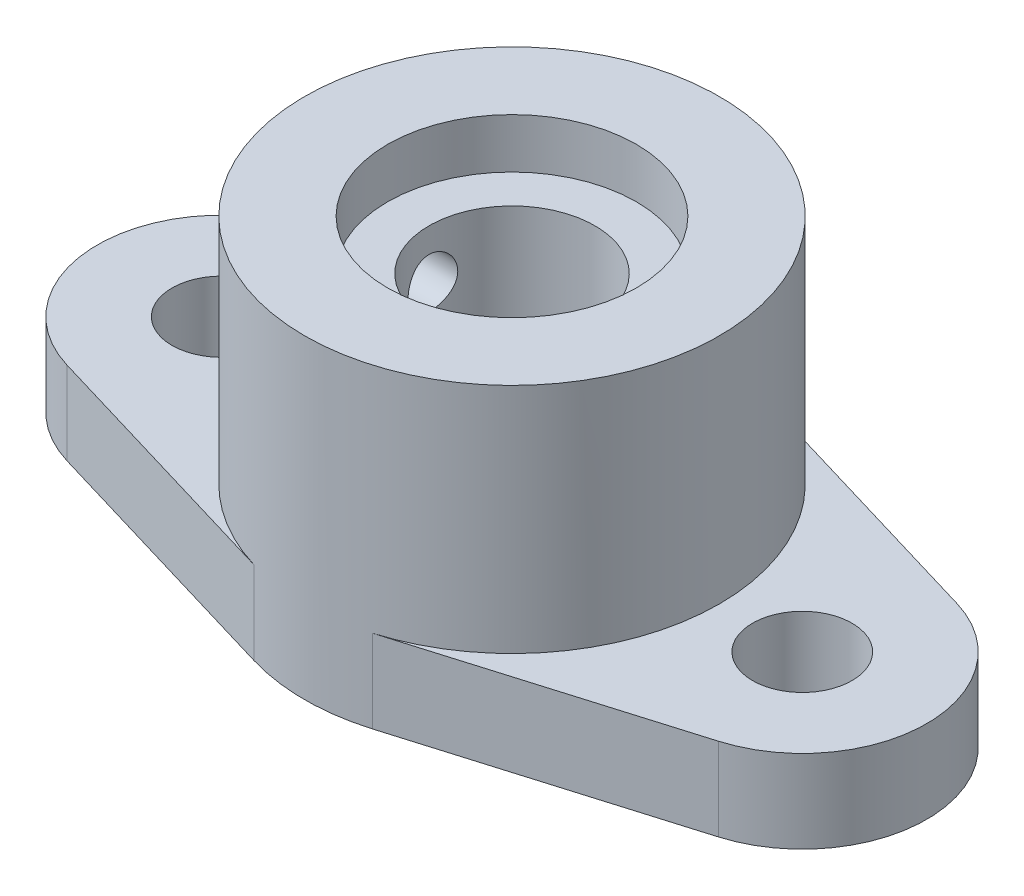
SolidWorks part; units mm, degrees
ref_plane "Front Plane" through (0, 0, 0) normal (0, 0, 1) x (1, 0, 0)
ref_plane "Top Plane" through (0, 0, 0) normal (0, 1, 0) x (1, 0, 0)
ref_plane "Right Plane" through (0, 0, 0) normal (1, 0, 0) x (0, 0, -1)
sketch "Sketch1" plane through (0, 0, 0) normal (0, 1, 0) x (1, 0, 0)
  line L0 (0, 44.7917) -> (0, -44.7917) construction
  line L1 (-56.9354, 0) -> (56.9354, 0) construction
  line L2 (-39.2857, 14.3747) -> (-7.1429, 23.9579)
  line L3 (-39.2857, -14.3747) -> (-7.1429, -23.9579)
  line L4 (39.2857, -14.3747) -> (7.1429, -23.9579)
  line L5 (39.2857, 14.3747) -> (7.1429, 23.9579)
  circle A0 centre (0, 0) radius 10
  circle A1 centre (0, 0) radius 15
  circle A2 centre (0, 0) radius 25
  circle A3 centre (-35, 0) radius 6
  circle A4 centre (35, 0) radius 6
  arc A5 (-39.2857, 14.3747) -> (-39.2857, -14.3747) centre (-35, 0) ccw
  arc A6 (39.2857, 14.3747) -> (39.2857, -14.3747) centre (35, 0) cw
  point P4 (0, 0)
  point P8 (0, 0)
  point P19 (0, 0)
  point P20 (0, 0)
  point P21 (0, 0)
  dimension "D1" = 20
  dimension "D2" = 30
  dimension "D3" = 50
  dimension "D4" = 12
  dimension "D6" = 30
  dimension "D5" = 70
extrude "Boss-Extrude1" add sketch "Sketch1" along normal blind 10 contours L2 A5 L3 A2 A3 | A6 L5 A2 L4 A4 region at (-23.0306, 0, -18.5502) region at (23.0306, 0, -18.5502)
extrude "Boss-Extrude2" add sketch "Sketch1<3>" along normal blind 38 contours A2 A1 region at (0, 0, -24.2929)
sketch "Sketch1<3>" plane through (0, 0, 0) normal (0, 1, 0) x (1, 0, 0) same geometry as "Sketch1"
extrude "Boss-Extrude3" add sketch "Sketch1<4>" along normal blind 32 contours A1 A0 region at (-14.5757, 0, 0)
sketch "Sketch1<4>" plane through (0, 0, 0) normal (0, 1, 0) x (1, 0, 0) same geometry as "Sketch1"
sketch "Sketch4" plane through (0, 0, 0) normal (1, 0, 0) x (0, 0, -1)
  line L0 (15, 38) -> (-15, 38) construction
  circle A0 centre (0, 26) radius 3
  dimension "D1" = 6
  dimension "D2" = 12
extrude "Cut-Extrude1" cut sketch "Sketch4" against normal blind 40
